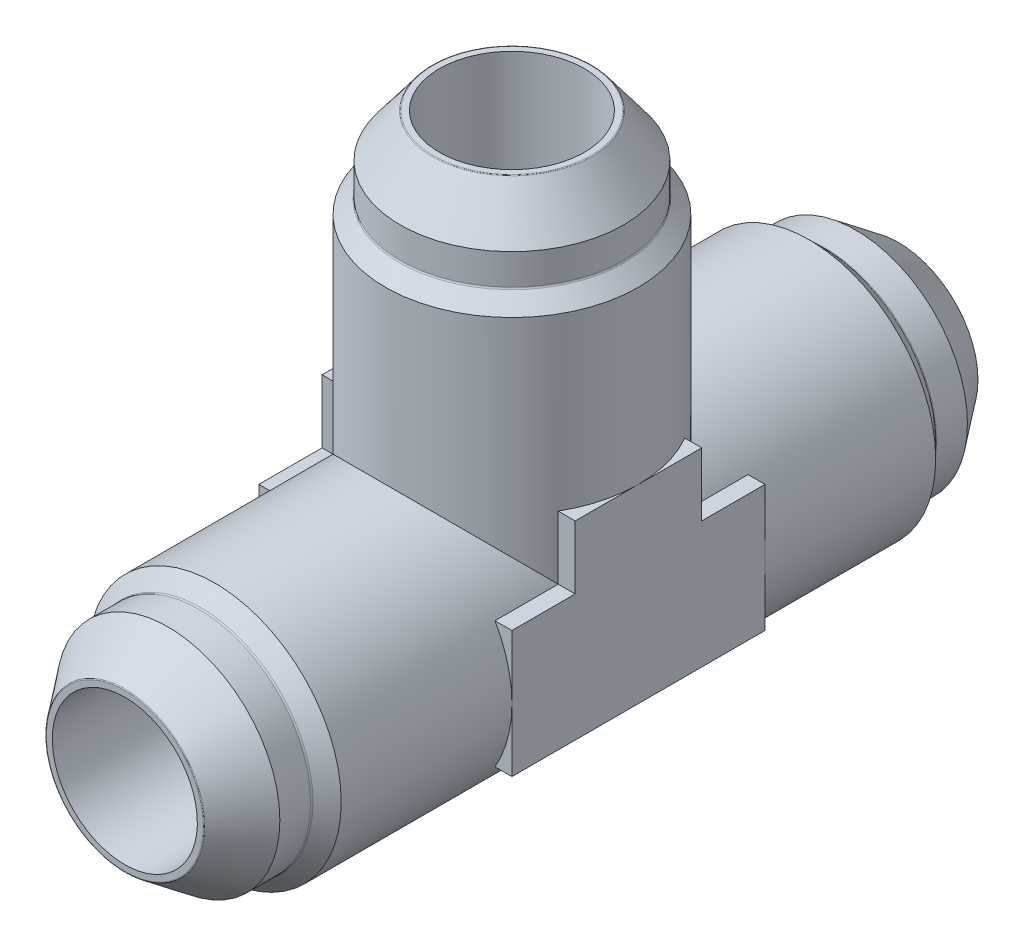
SolidWorks part; units mm, degrees
material "AISI 316 Stainless Steel Sheet (SS)"
ref_plane "Front Plane" through (0, 0, 0) normal (0, 0, 1) x (1, 0, 0)
ref_plane "Top Plane" through (0, 0, 0) normal (0, 1, 0) x (1, 0, 0)
ref_plane "Right Plane" through (0, 0, 0) normal (1, 0, 0) x (0, 0, -1)
sketch "Sketch0" plane through (0, 0, 0) normal (1, 0, 0) x (0, 0, -1)
  line L0 (-41.275, 0) -> (0, 0) construction
  line L1 (0, 0) -> (41.275, 0) construction
  line L2 (-33.274, 13.4937) -> (-33.274, -13.4937) construction
  line L3 (-41.275, 7.7343) -> (-41.275, -7.7343) construction
  line L4 (-41.275, 8.4328) -> (-41.275, -8.4328) construction
  line L5 (-36.6571, 11.9126) -> (-36.6571, -11.9126) construction
  line L6 (-41.275, 8.4328) -> (-36.6571, 11.9126) construction
  line L7 (-36.6571, 11.9126) -> (-33.274, 11.9126) construction
  line L8 (-33.274, 11.9126) -> (-33.274, -11.9126) construction
  line L9 (-19.3294, 17.4625) -> (-19.3294, -17.4625) construction
  line L10 (-19.3294, 17.2847) -> (-19.3294, -17.2847) construction
  line L11 (-33.274, 11.9126) -> (-33.274, 13.4937) construction
  line L12 (-33.274, 13.4937) -> (-22.5044, 13.4937) construction
  line L13 (-22.5044, 13.4937) -> (-22.5044, 12.0015) construction
  line L14 (-22.5044, 12.0015) -> (-19.3294, 12.0015) construction
  line L15 (-22.5044, 12.0015) -> (-22.5044, -12.0015) construction
  line L16 (-19.3294, 0) -> (-19.5326, 0) construction
  line L17 (0, 41.275) -> (0, 0) construction
  point P8 (-19.3294, 0)
  point P13 (-36.6571, 0)
  point P14 (-33.274, 0)
  point P24 (-22.5044, 0)
  dimension "37" = 37
sketch "Sketch1" plane through (0, 0, 0) normal (1, 0, 0) x (0, 0, -1)
  line L0 (-41.275, 0) -> (-19.3294, 0)
  line L1 (-41.275, 0) -> (-41.275, 8.3695)
  line L2 (-41.2244, 8.4709) -> (-36.6571, 11.9126)
  line L3 (-36.6571, 11.9126) -> (-33.3792, 11.9126)
  line L4 (-33.1996, 11.987) -> (-31.6929, 13.4937)
  line L5 (-31.6929, 13.4937) -> (-23.9967, 13.4937)
  line L6 (-23.9967, 13.4937) -> (-22.5788, 12.0759) construction
  line L7 (-22.3992, 12.0015) -> (-19.3294, 12.0015) construction
  line L8 (-19.3294, 12.0015) -> (-19.3294, 0)
  line L9 (-19.3294, 17.4625) -> (-19.3294, -17.4625) construction
  line L10 (-33.274, 13.4937) -> (-33.274, -13.4937) construction
  line L11 (-19.812, 0) -> (0, 0) construction
  line L12 (-41.275, 7.7343) -> (-41.275, -7.7343) construction
  line L13 (-33.274, 13.4937) -> (-22.5044, 13.4937) construction
  line L14 (-23.9967, 13.4937) -> (-19.3294, 13.4937)
  line L15 (-22.5044, 13.4937) -> (-22.5044, 12.0015) construction
  line L16 (-19.3294, 13.4937) -> (-19.3294, 12.0015)
  arc A0 (-41.275, 8.3695) -> (-41.2244, 8.4709) centre (-41.148, 8.3695) cw
  arc A1 (-33.3792, 11.9126) -> (-33.1996, 11.987) centre (-33.3792, 12.1666) ccw
  arc A2 (-22.5788, 12.0759) -> (-22.3992, 12.0015) centre (-22.3992, 12.2555) ccw construction
  point P27 (-41.275, 8.4328)
  point P30 (-33.274, 11.9126)
  point P33 (-22.5044, 12.0015)
  dimension "D1" = 0.127
  dimension "D2" = 0.254
  dimension "D3" = 45
  dimension "D4" = 45
revolve "Revolve1" add sketch "Sketch1" angle 360 about L11
sketch "Sketch2" plane through (0, 0, 41.275) normal (0, 0, 1) x (1, 0, 0)
  circle A0 centre (0, 0) radius 13.4938
  point P3 (0, 13.4937)
curve "Helix/Spiral1" pitch 2.1167 height 24.0623 turns 11.368 parameters "Pitch"=2.1167
sketch "Sketch3" plane through (0, 0, 0) normal (1, 0, 0) x (0, 0, -1)
  line L0 (-43.2594, 13.7229) -> (-42.201, 11.8898) construction
  line L1 (-42.201, 11.8898) -> (-41.1427, 13.7229) construction
  line L2 (-41.1427, 13.7229) -> (-43.2594, 13.7229) construction
  line L3 (-41.275, 13.4937) -> (-43.1271, 13.4937) construction
  line L4 (-42.201, 13.7229) -> (-42.201, 13.4937) construction
  line L5 (-42.4215, 12.2717) -> (-41.9806, 12.2717) construction
  line L6 (-42.201, 12.2717) -> (-42.201, 11.8898) construction
  line L7 (-43.1932, 13.6083) -> (-42.5318, 12.4626)
  line L8 (-43.1932, 13.6083) -> (-41.2089, 13.6083)
  line L9 (-41.2089, 13.6083) -> (-41.8703, 12.4626)
  line L10 (-42.201, 11.8898) -> (-42.201, -13.4938) construction
  line L11 (-42.201, -13.4938) -> (-40.0844, -13.4937) construction
  line L12 (-40.0844, -13.4937) -> (-37.9677, -13.4938) construction
  line L13 (-37.9677, -13.4938) -> (-35.851, -13.4937) construction
  line L14 (-35.851, -13.4937) -> (-33.7344, -13.4937) construction
  line L15 (-33.7344, -13.4937) -> (-31.6177, -13.4937) construction
  line L16 (-31.6177, -13.4937) -> (-29.501, -13.4937) construction
  line L17 (-29.501, -13.4937) -> (-27.3844, -13.4937) construction
  line L21 (-31.6929, -13.4937) -> (-19.3294, -13.4937) construction
  arc A0 (-42.5318, 12.4626) -> (-41.8703, 12.4626) centre (-42.201, 12.6536) ccw
  point P13 (-42.201, 13.6083)
sweep "Cut-Sweep1" [suppressed] cut profiles "Sketch3" path "Helix/Spiral1"
sketch "Sketch4" plane through (0, 0, 0) normal (1, 0, 0) x (0, 0, -1)
  line L0 (-19.3294, 0) -> (-19.3294, 13.4937)
  line L1 (-19.3294, 13.4937) -> (0, 13.4937)
  line L2 (0, 13.4937) -> (0, 0)
  line L3 (0, 0) -> (-19.3294, 0)
revolve "Revolve2" add sketch "Sketch4" angle 360 about L3
ref_axis "Axis1" through (-10.7739, 0, 0) along (1, 0, 0)
pattern_circular "CirPattern1" count 3 over 180 about axis through (-10.7739, 0, 0) along (1, 0, 0) reverse direction yes of bodies 114 103
combine bodies "Combine1" operation type add bodies to combine 105 109 114
sketch "Sketch5" plane through (0, 0, 0) normal (1, 0, 0) x (0, 0, -1)
  line L0 (0, 0) -> (0, -6.7469) construction
  line L1 (-6.7469, 13.4937) -> (6.7469, 13.4938)
  line L2 (-13.4937, 6.7469) -> (-13.4937, -6.7469)
  line L3 (-13.4937, -6.7469) -> (13.4937, -6.7469)
  line L4 (13.4937, 6.7469) -> (13.4937, -6.7469)
  line L5 (0, -6.7469) -> (0, -13.4937) construction
  line L6 (-13.4937, 6.7469) -> (-6.7469, 6.7469)
  line L7 (-6.7469, 6.7469) -> (-6.7469, 13.4937)
  line L8 (6.7469, 13.4938) -> (6.7469, 6.7469)
  line L9 (6.7469, 6.7469) -> (13.4937, 6.7469)
  line L10 (-6.7469, 6.7469) -> (-6.7469, -6.7469) construction
  line L11 (6.7469, -6.7469) -> (6.7469, 6.7469) construction
  line L12 (-6.7469, 6.7469) -> (6.7469, 6.7469) construction
  line L13 (0, 0) -> (0, 6.7469) construction
  line L14 (0, 0) -> (-6.7469, 0) construction
  line L15 (-6.7469, 0) -> (-13.4937, 0) construction
  line L16 (0, 13.4937) -> (0, 6.7469) construction
extrude "Boss-Extrude1" add sketch "Sketch5" along normal mid plane 26.9875
sketch "Sketch6" plane through (0, 0, 0) normal (1, 0, 0) x (0, 0, -1)
  line L0 (-41.275, 7.7343) -> (0, 7.7343)
  line L1 (7.7343, 0) -> (-41.275, 0)
  line L2 (-41.275, 0) -> (-41.275, 7.7343)
  arc A0 (0, 7.7343) -> (7.7343, 0) centre (0, 0) cw
revolve "Cut-Revolve1" cut sketch "Sketch6" angle 360 about L1
pattern_circular "CirPattern2" count 3 over 180 about axis through (-10.7739, 0, 0) along (1, 0, 0) of "Cut-Revolve1" reverse direction yes
equation "\"D3@Helix/Spiral1\" = \"Pitch@Helix/Spiral1\" + \"J@Sketch0\""
equation "\"P@Sketch3\" = \"Pitch@Helix/Spiral1\""
equation "\"H/8@Sketch3\" = \"H@Sketch3\" / 8"
equation "\"2/3H@Sketch3\" = 2/3 * \"H@Sketch3\""
equation "\"D1@Boss-Extrude1\" = \"Thread OD@Sketch0\""
